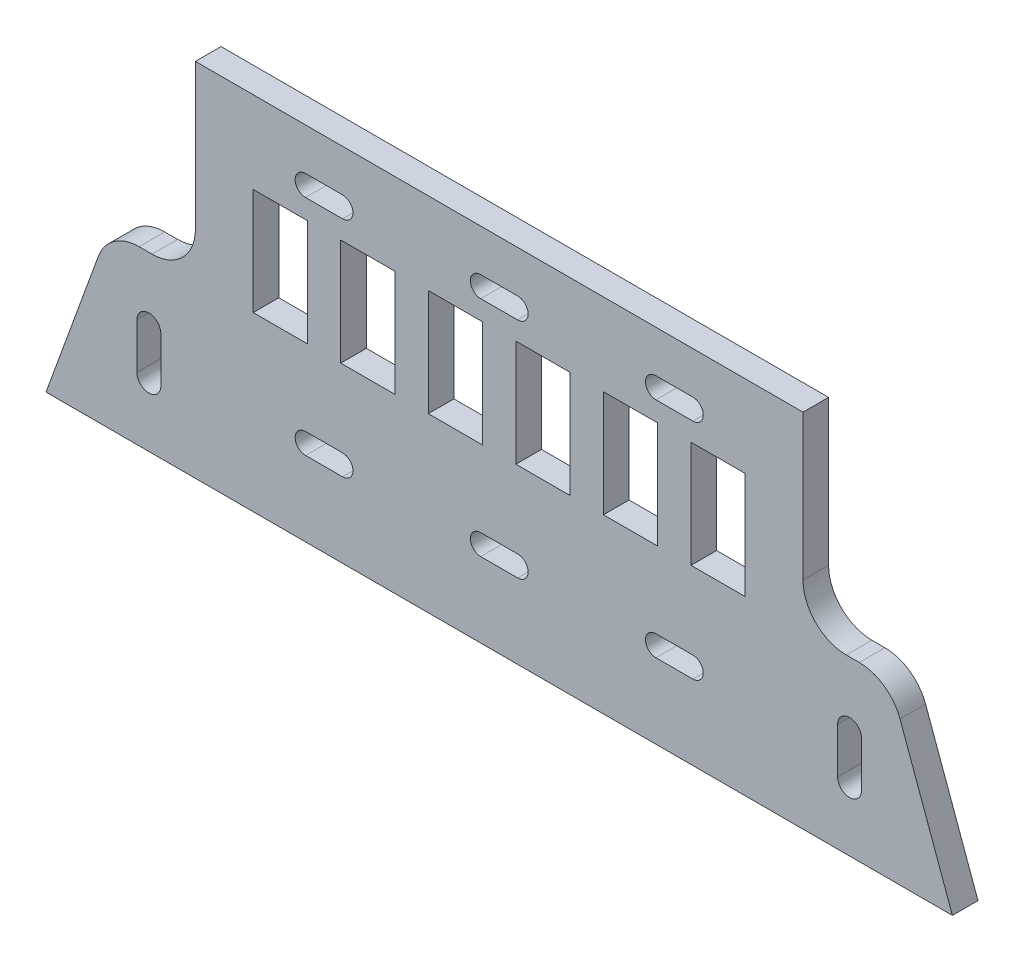
SolidWorks part; units mm, degrees
ref_plane "Front Plane" through (0, 0, 0) normal (0, 0, 1) x (1, 0, 0)
ref_plane "Top Plane" through (0, 0, 0) normal (0, 1, 0) x (1, 0, 0)
ref_plane "Right Plane" through (0, 0, 0) normal (1, 0, 0) x (0, 0, -1)
sketch "Sketch1" plane through (0, 0, 0) normal (0, 0, 1) x (1, 0, 0)
  line B0 (-99.2162, 110.081) -> (99.2162, 110.081)
  line B1 (-99.2162, 110.081) -> (-99.2162, 50.8)
  line B2 (-99.2162, 50.8) -> (99.2162, 50.8) construction
  line B3 (99.2162, 110.081) -> (99.2162, 50.8)
  line B4 (-99.2162, 50.8) -> (99.2162, 50.8)
  circle B5 centre (-77, 105.081) radius 1.5
  circle B6 centre (-77, 65.8) radius 1.5
  circle B7 centre (-92.3662, 65.8) radius 1.5
  circle B8 centre (-92.3662, 105.081) radius 1.5
  circle B9 centre (76.9662, 65.8) radius 1.5
  circle B10 centre (92.3662, 65.8) radius 1.5
  circle B11 centre (92.3662, 105.081) radius 1.5
  circle B12 centre (76.9662, 105.081) radius 1.5
  circle B13 centre (46.2, 105.081) radius 1.5
  circle B14 centre (46.2, 65.8) radius 1.5
  circle B15 centre (15.4, 65.8) radius 1.5
  circle B16 centre (15.4, 105.081) radius 1.5
  circle B17 centre (-15.4, 105.081) radius 1.5
  circle B18 centre (-15.4, 65.8) radius 1.5
  circle B19 centre (-46.2, 65.8) radius 1.5
  circle B20 centre (-46.2, 105.081) radius 1.5
sketch_block_instance "SideWallSketch-1"
sketch_block "SideWallSketch" parameters "D1"=10
extrude "Boss-Extrude1" add sketch "Sketch1" along normal blind 4.5 contours B1 B4 B3 B0 B20 B19 B18 B17 B16 B15 B14 B13 B12 B11 B10 B9 B8 B7 B6 B5 | B4 | B11 | B12 | B8 | B5 | B20 | B10 | B19 | B6 | B7 | B9 region at (0, 80.392, 0) region at (92.3662, 105.081, 0)
sketch "Sketch4" plane through (0, 0, 4.5) normal (0, 0, -1) x (-1, 0, 0)
  line L0 (-99.2162, 110.081) -> (-99.2162, 50.8) construction
  line L2 (99.2162, 110.081) -> (-99.2162, 110.081) construction
  line B0 (84.6831, 275.1313) -> (84.6831, 58.9036) construction
  line B1 (69.2831, 275.1313) -> (69.2831, 58.9036) construction
  line B2 (53.9169, 275.1313) -> (53.9169, 58.9036) construction
  line B3 (38.5169, 275.1313) -> (38.5169, 58.9036) construction
  line B4 (-84.6831, 275.1313) -> (-84.6831, 58.9036) construction
  line B5 (23.1169, 275.1313) -> (23.1169, 58.9036) construction
  line B6 (7.7169, 275.1313) -> (7.7169, 58.9036) construction
  line B7 (-7.6831, 275.1313) -> (-7.6831, 58.9036) construction
  line B8 (-23.0831, 275.1313) -> (-23.0831, 58.9036) construction
  line B9 (-38.4831, 275.1313) -> (-38.4831, 58.9036) construction
  line B10 (-53.8831, 275.1313) -> (-53.8831, 58.9036) construction
  line B11 (-69.2831, 275.1313) -> (-69.2831, 58.9036) construction
  line B12 (-81.8373, 96.8722) -> (-81.8373, 84.1222) construction
  line B13 (-89.4489, 99.8787) -> (-79.9173, 99.8787)
  line B14 (-89.4489, 99.8787) -> (-89.4489, 81.1287)
  line B15 (-89.4489, 81.1287) -> (-79.9173, 81.1287)
  line B16 (-79.9173, 99.8787) -> (-79.9173, 81.1287)
  line B17 (-89.4489, 99.8787) -> (-79.9173, 81.1287) construction
  line B18 (-89.4489, 81.1287) -> (-79.9173, 99.8787) construction
  line B19 (-74.052, 99.8787) -> (-64.5204, 99.8787)
  line B20 (-74.052, 99.8787) -> (-74.052, 81.1287)
  line B21 (-74.052, 81.1287) -> (-64.5204, 81.1287)
  line B22 (-64.5204, 99.8787) -> (-64.5204, 81.1287)
  line B23 (-66.4404, 96.8722) -> (-66.4404, 84.1222) construction
  line B24 (-74.052, 99.8787) -> (-64.5204, 81.1287) construction
  line B25 (-74.052, 81.1287) -> (-64.5204, 99.8787) construction
  line B26 (-58.6551, 99.8787) -> (-49.1234, 99.8787)
  line B27 (-58.6551, 99.8787) -> (-58.6551, 81.1287)
  line B28 (-58.6551, 81.1287) -> (-49.1234, 81.1287)
  line B29 (-49.1234, 99.8787) -> (-49.1234, 81.1287)
  line B30 (-51.0434, 96.8722) -> (-51.0434, 84.1222) construction
  line B31 (-58.6551, 99.8787) -> (-49.1234, 81.1287) construction
  line B32 (-58.6551, 81.1287) -> (-49.1234, 99.8787) construction
  line B33 (-43.2581, 99.8787) -> (-33.7265, 99.8787)
  line B34 (-43.2581, 99.8787) -> (-43.2581, 81.1287)
  line B35 (-43.2581, 81.1287) -> (-33.7265, 81.1287)
  line B36 (-33.7265, 99.8787) -> (-33.7265, 81.1287)
  line B37 (-35.6465, 96.8722) -> (-35.6465, 84.1222) construction
  line B38 (-43.2581, 99.8787) -> (-33.7265, 81.1287) construction
  line B39 (-43.2581, 81.1287) -> (-33.7265, 99.8787) construction
  line B40 (-27.8612, 99.8787) -> (-18.3296, 99.8787)
  line B41 (-27.8612, 99.8787) -> (-27.8612, 81.1287)
  line B42 (-27.8612, 81.1287) -> (-18.3296, 81.1287)
  line B43 (-18.3296, 99.8787) -> (-18.3296, 81.1287)
  line B44 (-20.2496, 96.8722) -> (-20.2496, 84.1222) construction
  line B45 (-27.8612, 99.8787) -> (-18.3296, 81.1287) construction
  line B46 (-27.8612, 81.1287) -> (-18.3296, 99.8787) construction
  line B47 (-12.4643, 99.8787) -> (-2.9326, 99.8787)
  line B48 (-12.4643, 99.8787) -> (-12.4643, 81.1287)
  line B49 (-12.4643, 81.1287) -> (-2.9326, 81.1287)
  line B50 (-2.9326, 99.8787) -> (-2.9326, 81.1287)
  line B51 (-4.8526, 96.8722) -> (-4.8526, 84.1222) construction
  line B52 (-12.4643, 99.8787) -> (-2.9326, 81.1287) construction
  line B53 (-12.4643, 81.1287) -> (-2.9326, 99.8787) construction
  line B54 (2.9326, 99.8787) -> (12.4643, 99.8787)
  line B55 (2.9326, 99.8787) -> (2.9326, 81.1287)
  line B56 (2.9326, 81.1287) -> (12.4643, 81.1287)
  line B57 (12.4643, 99.8787) -> (12.4643, 81.1287)
  line B58 (10.5443, 96.8722) -> (10.5443, 84.1222) construction
  line B59 (2.9326, 99.8787) -> (12.4643, 81.1287) construction
  line B60 (2.9326, 81.1287) -> (12.4643, 99.8787) construction
  line B61 (18.3296, 99.8787) -> (27.8612, 99.8787)
  line B62 (18.3296, 99.8787) -> (18.3296, 81.1287)
  line B63 (18.3296, 81.1287) -> (27.8612, 81.1287)
  line B64 (27.8612, 99.8787) -> (27.8612, 81.1287)
  line B65 (25.9412, 96.8722) -> (25.9412, 84.1222) construction
  line B66 (18.3296, 99.8787) -> (27.8612, 81.1287) construction
  line B67 (18.3296, 81.1287) -> (27.8612, 99.8787) construction
  line B68 (33.7265, 99.8787) -> (43.2581, 99.8787)
  line B69 (33.7265, 99.8787) -> (33.7265, 81.1287)
  line B70 (33.7265, 81.1287) -> (43.2581, 81.1287)
  line B71 (43.2581, 99.8787) -> (43.2581, 81.1287)
  line B72 (41.3381, 96.8722) -> (41.3381, 84.1222) construction
  line B73 (33.7265, 99.8787) -> (43.2581, 81.1287) construction
  line B74 (33.7265, 81.1287) -> (43.2581, 99.8787) construction
  line B75 (49.1234, 99.8787) -> (58.6551, 99.8787)
  line B76 (49.1234, 99.8787) -> (49.1234, 81.1287)
  line B77 (49.1234, 81.1287) -> (58.6551, 81.1287)
  line B78 (58.6551, 99.8787) -> (58.6551, 81.1287)
  line B79 (56.7351, 96.8722) -> (56.7351, 84.1222) construction
  line B80 (49.1234, 99.8787) -> (58.6551, 81.1287) construction
  line B81 (49.1234, 81.1287) -> (58.6551, 99.8787) construction
  line B82 (64.5204, 99.8787) -> (74.052, 99.8787)
  line B83 (64.5204, 99.8787) -> (64.5204, 81.1287)
  line B84 (64.5204, 81.1287) -> (74.052, 81.1287)
  line B85 (74.052, 99.8787) -> (74.052, 81.1287)
  line B86 (72.132, 96.8722) -> (72.132, 84.1222) construction
  line B87 (64.5204, 99.8787) -> (74.052, 81.1287) construction
  line B88 (64.5204, 81.1287) -> (74.052, 99.8787) construction
  line B89 (79.9173, 99.8787) -> (89.4489, 99.8787)
  line B90 (79.9173, 99.8787) -> (79.9173, 81.1287)
  line B91 (79.9173, 81.1287) -> (89.4489, 81.1287)
  line B92 (89.4489, 99.8787) -> (89.4489, 81.1287)
  line B93 (87.5289, 96.8722) -> (87.5289, 84.1222) construction
  line B94 (79.9173, 99.8787) -> (89.4489, 81.1287) construction
  line B95 (79.9173, 81.1287) -> (89.4489, 99.8787) construction
  line B96 (-99.2162, 110.081) -> (99.2162, 110.081) construction
  line B97 (-99.2162, 110.081) -> (-99.2162, 0) construction
  line B98 (-99.2162, 0) -> (99.2162, 0) construction
  line B99 (99.2162, 110.081) -> (99.2162, 0) construction
sketch_block_instance "Block2-1"
sketch_block "Block2"
extrude "Cut-Extrude2" cut sketch "Sketch4" along normal through all contours B26 B29 B28 B27 | B33 B36 B35 B34 | B40 B43 B42 B41 | B47 B50 B49 B48 | B54 B57 B56 B55 | B61 B64 B63 B62 region at (53.8893, 90.5037, 4.5) region at (38.4923, 90.5037, 4.5) region at (23.0954, 90.5037, 4.5) region at (7.6985, 90.5037, 4.5) region at (-7.6985, 90.5037, 4.5) region at (-23.0954, 90.5037, 4.5)
sketch "Sketch5" plane through (0, 0, 0) normal (0, 0, -1) x (-1, 0, 0)
  line L0 (-79.1, 65.8) -> (-46.2, 65.8) construction
  line L1 (-77, 69.8) -> (-77, 61.8) construction
  line L2 (-74.9, 69.8) -> (-74.9, 61.8)
  line L3 (-79.1, 69.8) -> (-79.1, 61.8)
  line L4 (-15.4, 110.081) -> (-15.4, 50.8) construction
  line L5 (99.2162, 110.081) -> (-99.2162, 110.081) construction
  line L6 (99.2162, 50.8) -> (-99.2162, 50.8) construction
  line L7 (46.2, 69.8) -> (46.2, 61.8) construction
  line L8 (44.1, 69.8) -> (44.1, 61.8)
  line L9 (48.3, 69.8) -> (48.3, 61.8)
  circle A0 centre (-46.2, 65.8) radius 1.5 construction
  arc A1 (44.1, 69.8) -> (48.3, 69.8) centre (46.2, 69.8) cw
  circle A2 centre (-77, 65.8) radius 2.1 construction
  arc A3 (-74.9, 69.8) -> (-79.1, 69.8) centre (-77, 69.8) ccw
  arc A4 (-79.1, 61.8) -> (-74.9, 61.8) centre (-77, 61.8) ccw
  arc A5 (48.3, 61.8) -> (44.1, 61.8) centre (46.2, 61.8) cw
  circle A6 centre (46.2, 65.8) radius 2.1 construction
  point P10 (-77, 65.8)
  point P23 (46.2, 65.8)
  dimension "D1" = 4.2
  dimension "D2" = 8
  dimension "D3" = 61.6
extrude "Cut-Extrude3" cut sketch "Sketch5" against normal through all contours L3 A4 L2 A3 | A5 L9 A1 L8 region at (77, 65.8, 0) region at (-46.2, 65.8, 0)
sketch "Sketch6" plane through (0, 0, 0) normal (0, 0, -1) x (-1, 0, 0)
  line L0 (99.2162, 110.081) -> (99.2162, 50.8) construction
  line L1 (-99.2162, 110.081) -> (99.2162, 110.081)
  line L2 (-99.2162, 110.081) -> (-99.2162, 114.301)
  line L3 (-99.2162, 114.301) -> (99.2162, 114.301)
  line L4 (99.2162, 110.081) -> (99.2162, 114.301)
  dimension "D1" = 4.22
extrude "Boss-Extrude2" add sketch "Sketch6" against normal up to surface (4.5 mm away) up to face at (77, 65.8, 4.5)
sketch "Sketch7" plane through (0, 0, 0) normal (0, 0, -1) x (-1, 0, 0)
  line L0 (-58.6551, 81.1287) -> (-49.1234, 81.1287) construction
  line L1 (-99.2162, 114.301) -> (99.2162, 114.301)
  line L2 (-99.2162, 114.301) -> (-99.2162, 50.8)
  line L3 (-99.2162, 50.8) -> (99.2162, 50.8)
  line L4 (99.2162, 114.301) -> (99.2162, 50.8)
  line L5 (-99.2162, 114.301) -> (99.2162, 50.8) construction
  line L6 (-99.2162, 50.8) -> (99.2162, 114.301) construction
  line L7 (-84.0501, 81.1287) -> (-68.8151, 81.1287)
  line L8 (-68.8151, 81.1287) -> (-68.8151, 114.301)
  line L9 (-84.0501, 81.1287) -> (-95.0889, 50.8)
  line L10 (-58.6551, 99.8787) -> (-58.6551, 81.1287) construction
  line L11 (-15.4, 114.301) -> (-15.4, 50.8) construction
  line L12 (99.2162, 114.301) -> (-99.2162, 114.301) construction
  line L14 (53.2501, 81.1287) -> (64.2889, 50.8)
  line L15 (38.0151, 81.1287) -> (38.0151, 114.301)
  line L16 (53.2501, 81.1287) -> (38.0151, 81.1287)
  point P4 (0, 82.5505)
  line M9 (99.2162, 50.8) -> (99.2162, 114.301)
  line M10 (99.2162, 114.301) -> (-99.2162, 114.301)
  line M11 (-99.2162, 114.301) -> (-99.2162, 50.8)
  line M12 (-99.2162, 50.8) -> (99.2162, 50.8)
  dimension "D1" = 10.16
  dimension "D2" = 70
extrude "Cut-Extrude4" cut sketch "Sketch7" against normal through all contours L9 L7 L8 L1 M11 M12 | L16 L14 L15 M12 M9 M10 region at (86.2309, 91.2253, 0) region at (-72.4769, 86.0159, 0)
fillet "Fillet1" radius 7.62 4 edges at (-53.2501, 81.1287, 2.25) (-38.0151, 81.1287, 2.25) (68.8151, 81.1287, 2.25) (84.0501, 81.1287, 2.25)
hole_wizard "#27 (0.144) Diameter Slot1" positions "Sketch8" profile "Sketch9" size "#27" standard "ANSI Inch" slot yes end condition through all
sketch "Sketch8" plane through (0, 0, 0) normal (0, 0, -1) x (-1, 0, 0)
  line L3 (-41.12, 65.8) -> (-51.28, 65.8) construction
  point P0 (-46.2, 65.8)
  point P5 (-15.4, 65.8)
  point P8 (15.4, 65.8)
  point P11 (15.4, 105.081)
  point P14 (-15.4, 105.081)
  point P17 (-46.2, 105.081)
  dimension "D1" = 10.16
sketch "Sketch9" plane through (46.2, 65.8, 0) normal (1, 0, 0) x (0, 1, 0)
  line L0 (0, 0) -> (0, 4.5)
  line L1 (0, 4.5) -> (1.8288, 4.5)
  line L2 (1.8288, 4.5) -> (1.8288, 0)
  line L5 (1.8288, 0) -> (0, 0)
  line L11 (0, -6.35) -> (0, 107.95) construction
  dimension "Thru Hole Dia." = 3.6576
  dimension "Thru Hole Depth" = 4.5
